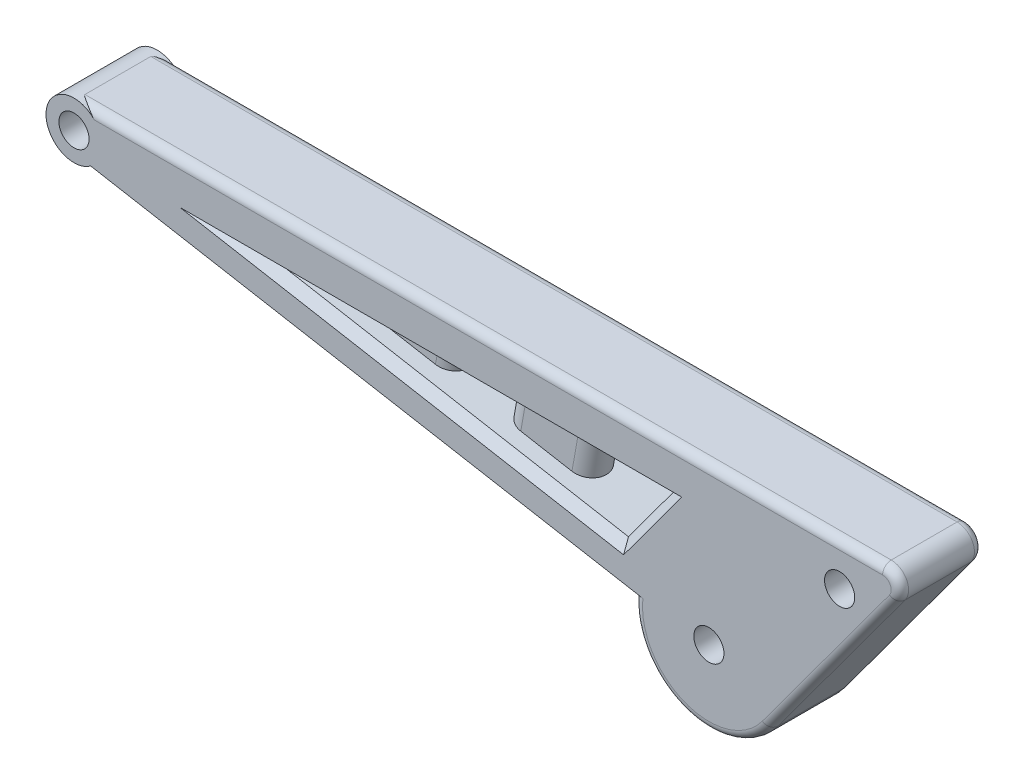
SolidWorks part; units mm, degrees
ref_plane "Front Plane" through (0, 0, 0) normal (0, 0, 1) x (1, 0, 0)
ref_plane "Top Plane" through (0, 0, 0) normal (0, 1, 0) x (1, 0, 0)
ref_plane "Right Plane" through (0, 0, 0) normal (1, 0, 0) x (0, 0, -1)
sketch "Sketch3" plane through (0, 0, 0) normal (0, 0, 1) x (1, 0, 0)
  line L0 (119.1398, 14.5365) -> (82.4405, -35.3342)
  line L1 (-117.5, 22.5) -> (115.1126, 22.5)
  line L5 (0, 0) -> (95.7584, -17.2365) construction
  line L6 (-125, -22.5) -> (125, 22.5) construction
  line L7 (-118.8158, 6.3979) -> (43.3462, -22.5)
  arc A0 (43.3462, -22.5) -> (82.4405, -35.3342) centre (65, -22.5) ccw
  arc A1 (119.1398, 14.5365) -> (115.1126, 22.5) centre (115.1126, 17.5) ccw
  arc A4 (-118.8158, 6.3979) -> (-117.5, 22.5) centre (-118.1579, 14.449) cw
  point P0 (0, 0)
  point P15 (-125, 7.5)
  dimension "D1" = 5
extrude "Boss-Extrude1" add sketch "Sketch3" along normal blind 24
sketch "Sketch4" plane through (0, 0, 24) normal (0, 0, 1) x (1, 0, 0)
  line L1 (-73.4353, 10.5) -> (39.3055, -9.5909)
  line L2 (82.4405, -35.3342) -> (119.1398, 14.5365) construction
  line L4 (39.3055, -9.5909) -> (54.0901, 10.5)
  line L5 (54.0901, 10.5) -> (-73.4353, 10.5)
  line L6 (-118.8158, 6.3979) -> (43.3462, -22.5) construction
  line L7 (115.1126, 22.5) -> (-117.5, 22.5) construction
  circle A0 centre (65, -22.5) radius 4.35
  circle A1 centre (102.7203, 10.3204) radius 4.35
  circle A3 centre (-118.1579, 14.449) radius 4.35
  circle A4 centre (65, -22.5) radius 21.6538 construction
  dimension "D1" = 50
  dimension "D3" = 12
  dimension "D2" = 8.7
  dimension "D6" = 8.7
  dimension "D7" = 8.7
  dimension "D4" = 12
  dimension "D5" = 50
extrude "Cut-Extrude1" cut sketch "Sketch4" against normal blind 24
sketch "Sketch7" plane through (-0.4467, -2.5069, 0) normal (0.1754, 0.9845, 0) x (0.9845, -0.1754, 0)
  line L0 (-16.88, -24) -> (-16.88, 0) construction
  line L1 (-74.1384, -24) -> (40.3785, -24) construction
  line L2 (-74.1384, 0) -> (40.3785, 0) construction
  line L3 (19.25, -12) -> (4.25, -12) construction
  line L4 (19.25, -17) -> (4.25, -17)
  line L5 (19.25, -7) -> (4.25, -7)
  line L11 (-20.75, -7) -> (-35.75, -7)
  line L12 (-20.75, -17) -> (-35.75, -17)
  line L13 (-20.75, -12) -> (-35.75, -12) construction
  arc A0 (19.25, -17) -> (19.25, -7) centre (19.25, -12) ccw
  arc A1 (4.25, -7) -> (4.25, -17) centre (4.25, -12) ccw
  arc A6 (-20.75, -17) -> (-20.75, -7) centre (-20.75, -12) ccw
  arc A7 (-35.75, -7) -> (-35.75, -17) centre (-35.75, -12) ccw
  point P8 (11.75, -12)
  point P13 (-16.88, -12)
  point P17 (-28.25, -12)
  dimension "D1" = 10
  dimension "D2" = 15
  dimension "D3" = 28.63
  dimension "D4" = 2
extrude "Boss-Extrude2" add sketch "Sketch7" along normal up to surface (13.9692 mm away) up to face at (-9.6726, 10.5, 12)
fillet "Fillet1" radius 2.5 8 edges at (58.2459, -43.0736, 0) (100.7901, -10.3989, 0) (119.5746, 19.7564, 0) (58.2459, -43.0736, 24) (100.7901, -10.3989, 24) (119.5746, 19.7564, 24) (-1.1937, 22.5, 0) (-1.1937, 22.5, 24)
chamfer "Chamfer1" distance 2.5 angle 45 6 edges at (-36.4822, -8.2742, 0) (-36.4822, -8.2742, 24) (46.6978, 0.4546, 0) (-17.0649, 0.4546, 0) (46.6978, 0.4546, 24) (-17.0649, 0.4546, 24)
